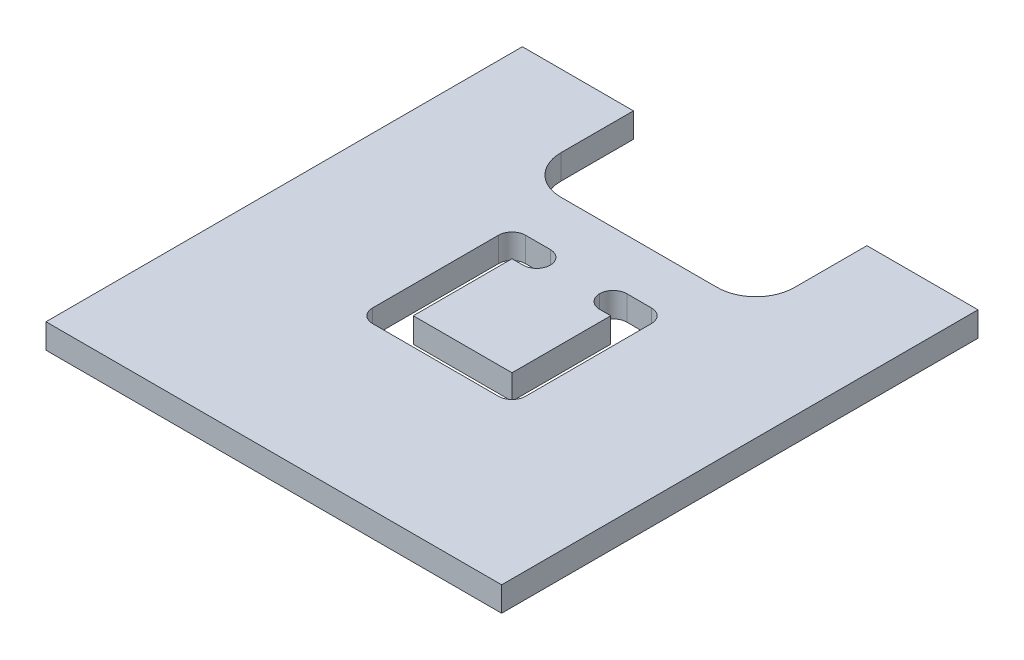
SolidWorks part; units mm, degrees
ref_plane "前视基准面" through (0, 0, 0) normal (0, 0, 1) x (1, 0, 0)
ref_plane "上视基准面" through (0, 0, 0) normal (0, 1, 0) x (1, 0, 0)
ref_plane "右视基准面" through (0, 0, 0) normal (1, 0, 0) x (0, 0, -1)
sketch "草图1" plane through (0, 0, 0) normal (0, 1, 0) x (1, 0, 0)
  line L1 (-9.23, -9.65) -> (9.23, -9.65)
  line L2 (-9.23, -9.65) -> (-9.23, 9.65)
  line L3 (-9.23, 9.65) -> (9.23, 9.65)
  line L4 (9.23, -9.65) -> (9.23, 9.65)
  line L5 (-9.23, -9.65) -> (9.23, 9.65) construction
  line L6 (-9.23, 9.65) -> (9.23, -9.65) construction
  point P0 (0, 0)
  dimension "D1" = 18.46
  dimension "D2" = 19.3
extrude "凸台-拉伸1" add sketch "草图1" along normal blind 1
sketch "草图2" plane through (0, 0, 0) normal (0, -1, 0) x (1, 0, 0)
  line L0 (9.23, -9.65) -> (-9.23, -9.65) construction
  line L1 (4.73, -9.65) -> (-4.73, -9.65)
  line L2 (4.73, -9.65) -> (4.73, -5.15)
  line L3 (4.73, -5.15) -> (-4.73, -5.15)
  line L4 (-4.73, -9.65) -> (-4.73, -5.15)
  line L5 (-4.73, -9.65) -> (-4.73, -5.15) construction
  line L6 (4.73, -5.15) -> (4.73, -9.65) construction
  line L7 (-9.23, -5.15) -> (-4.73, -5.15) construction
extrude "切除-拉伸1" cut sketch "草图2" against normal through all
fillet "圆角1" radius 1.56 2 edges at (-4.73, 0.5, -5.15) (4.73, 0.5, -5.15)
sketch "草图3" plane through (0, 1, 0) normal (0, 1, 0) x (1, 0, 0)
  line L0 (1, 3.1) -> (3.1, 3.1)
  line L1 (-2, -2) -> (2, -2)
  line L2 (-2, -2) -> (-2, 2)
  line L4 (2, -2) -> (2, 2)
  line L5 (-2, -2) -> (2, 2) construction
  line L6 (-2, 2) -> (2, -2) construction
  line L7 (-3.1, -3.1) -> (3.1, -3.1)
  line L8 (-3.1, -3.1) -> (-3.1, 3.1)
  line L9 (-3.1, 3.1) -> (-1, 3.1)
  line L10 (3.1, -3.1) -> (3.1, 3.1)
  line L11 (-3.1, -3.1) -> (3.1, 3.1) construction
  line L12 (-3.1, 3.1) -> (3.1, -3.1) construction
  line L13 (-2, 2) -> (-1, 2)
  line L14 (-1, 2) -> (-1, 3.1)
  line L15 (2, 2) -> (1, 2)
  line L16 (1, 2) -> (1, 3.1)
  line L17 (-1, 2.55) -> (1, 2.55) construction
  line L18 (1, 2.55) -> (0, 2.55) construction
  line L19 (0, 2.55) -> (0, 0) construction
  point P0 (0, 0)
  point P6 (0, 0)
  point P11 (0, 0)
  dimension "D1" = 4
  dimension "D2" = 4
  dimension "D3" = 1.1
  dimension "D4" = 1.1
  dimension "D5" = 2
extrude "切除-拉伸2" cut sketch "草图3" against normal through all
fillet "圆角7" radius 0.55 8 edges at (-1, 0.5, -2) (1, 0.5, -2) (-3.1, 0.5, 3.1) (-1, 0.5, -3.1) (-3.1, 0.5, -3.1) (1, 0.5, -3.1) (3.1, 0.5, -3.1) (3.1, 0.5, 3.1)
ref_plane "基准面1" through (0, 0, 0) normal (-1, 0, 0) x (0, 0, 1)
ref_plane "基准面2" through (0, 0, 0) normal (0, 0, -1) x (-1, 0, 0)
